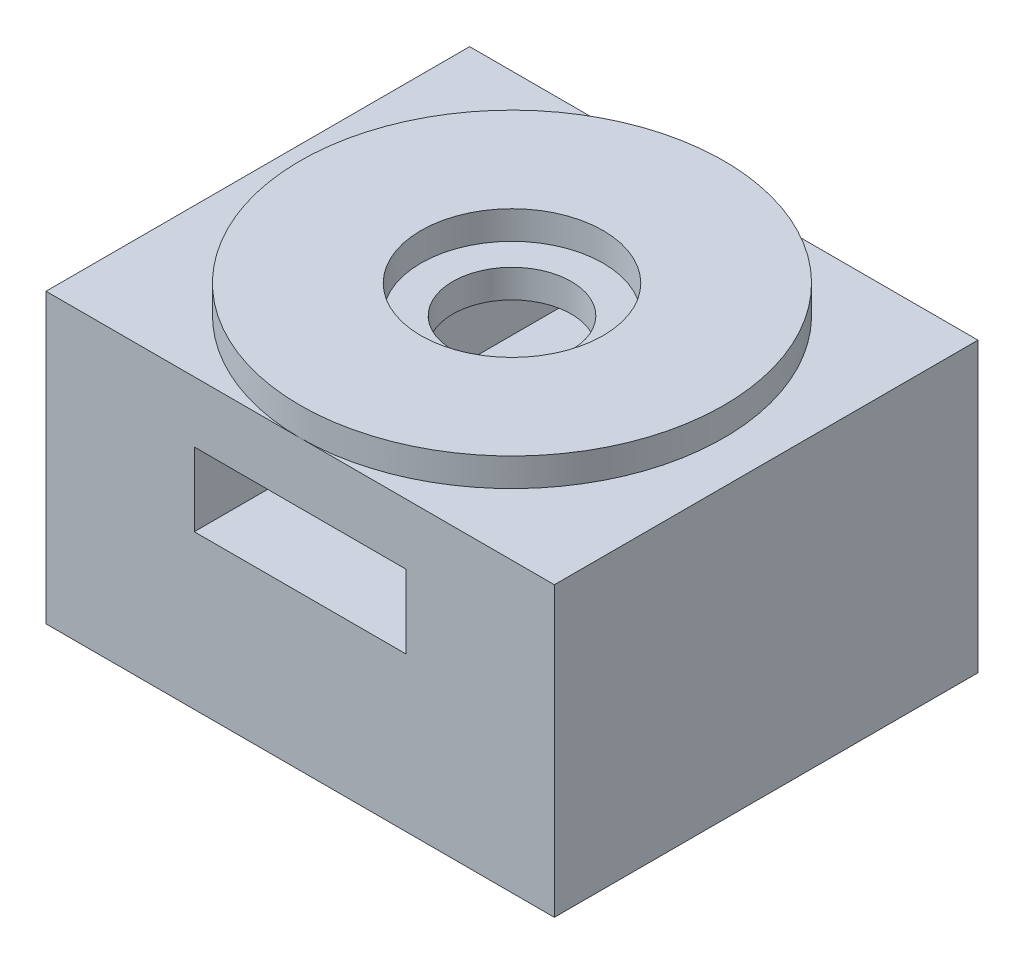
SolidWorks part; units mm, degrees
ref_plane "Front Plane" through (0, 0, 0) normal (0, 0, 1) x (1, 0, 0)
ref_plane "Top Plane" through (0, 0, 0) normal (0, 1, 0) x (1, 0, 0)
ref_plane "Right Plane" through (0, 0, 0) normal (1, 0, 0) x (0, 0, -1)
sketch "Sketch1" plane through (0, 0, 0) normal (0, 1, 0) x (1, 0, 0)
  line L0 (-9, 7.5) -> (9, -7.5) construction
  line L1 (-9, 7.5) -> (9, 7.5)
  line L2 (-9, 7.5) -> (-9, -7.5)
  line L3 (-9, -7.5) -> (9, -7.5)
  line L4 (9, 7.5) -> (9, -7.5)
  circle A0 centre (0, 0) radius 2.1
  circle A2 centre (0, 0) radius 1.9 construction
  dimension "D3" = 0.2
  dimension "D1" = 18
  dimension "D2" = 15
extrude "Boss-Extrude1" add sketch "Sketch1" along normal blind 5.1 and the other way blind 5.1
sketch "Sketch4" plane through (0, 0, 0) normal (0, 1, 0) x (1, 0, 0)
  line L0 (-3.4, 3.6) -> (3.4, -3.6) construction
  line L1 (-3.4, 3.6) -> (3.4, 3.6)
  line L2 (-3.4, 3.6) -> (-3.4, -3.6)
  line L3 (-3.4, -3.6) -> (3.4, -3.6)
  line L4 (3.4, 3.6) -> (3.4, -3.6)
  dimension "D1" = 6.8
  dimension "D2" = 7.2
extrude "Cut-Extrude1" cut sketch "Sketch4" against normal offset from surface 1 and the other way offset from surface 1 up to face at (0, -5.1, 2.1) other way up to face at (0, 5.1, 0)
sketch "Sketch5" plane through (0, 0, -7.5) normal (0, 0, -1) x (-1, 0, 0)
  line L0 (0, 0) -> (0, -7.0196) construction
  line L1 (1.75, -0.4) -> (4.9, -0.4)
  line L3 (-1.75, -4.1) -> (1.75, -4.1)
  line L5 (-9, -5.1) -> (9, -5.1) construction
  line L6 (-1.75, -4.1) -> (-1.75, -0.4)
  line L7 (-9, 5.1) -> (9, 5.1) construction
  line L8 (1.75, -0.4) -> (1.75, -4.1)
  line L12 (-4.9, 4.1) -> (4.9, 4.1)
  line L13 (-4.9, 4.1) -> (-4.9, -0.4)
  line L14 (-4.9, -0.4) -> (-1.75, -0.4)
  line L15 (4.9, 4.1) -> (4.9, -0.4)
  point P5 (-1.2046, 2.0199)
  point P6 (0.8649, 2.0171)
  point P13 (0, -4.1)
  point P21 (-4.825, 3.4044)
  dimension "D3" = 1
  dimension "D4" = 3.5
  dimension "D5" = 1
  dimension "D6" = 9.8
  dimension "D7" = 4.5
extrude "Cut-Extrude2" cut sketch "Sketch5" against normal blind 7.5
sketch "Sketch6" plane through (0, 4.1, 0) normal (0, -1, 0) x (1, 0, 0)
  line L0 (-4.9, 0) -> (-4.9, -7.5) construction
  circle A0 centre (0, 0) radius 4.9
extrude "Cut-Extrude4" cut sketch "Sketch6" along normal up to surface (4.5 mm away) up to face at (3.35, -0.4, -3.7)
sketch "Sketch7" plane through (0, 5.1, 0) normal (0, 1, 0) x (1, 0, 0)
  line L0 (9, 7.5) -> (-9, 7.5) construction
  circle A0 centre (0, 0) radius 3.225
  circle A1 centre (0, 0) radius 7.5
  dimension "D2" = 6.45
extrude "Boss-Extrude2" add sketch "Sketch7" along normal blind 1
sketch "Sketch8" plane through (0, 0, 7.5) normal (0, 0, 1) x (1, 0, 0)
  line L0 (0, -0.1873) -> (0, -2.6664) construction
  line L1 (-3.75, 2.95) -> (3.75, 2.95)
  line L2 (-3.75, 2.95) -> (-3.75, 0.35)
  line L3 (-3.75, 0.35) -> (3.75, 0.35)
  line L4 (3.75, 2.95) -> (3.75, 0.35)
  line L5 (-9, 5.1) -> (0, 5.1) construction
  line L7 (3.3242, -0.4) -> (-3.3242, -0.4) construction
  point P5 (0, 2.95)
  dimension "D1" = 7.5
  dimension "D2" = 0.75
  dimension "D3" = 2.15
extrude "Cut-Extrude5" cut sketch "Sketch8" against normal blind 6.5
